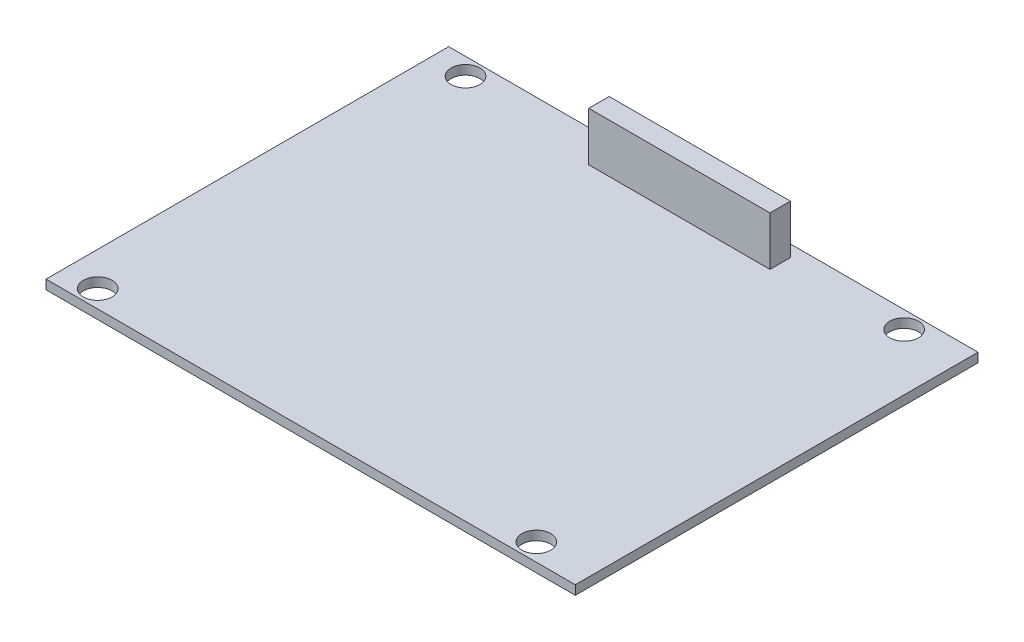
SolidWorks part; units mm, degrees
ref_plane "Front Plane" through (0, 0, 0) normal (0, 0, 1) x (1, 0, 0)
ref_plane "Top Plane" through (0, 0, 0) normal (0, 1, 0) x (1, 0, 0)
ref_plane "Right Plane" through (0, 0, 0) normal (1, 0, 0) x (0, 0, -1)
sketch "Sketch1" plane through (0, 0, 0) normal (0, 1, 0) x (1, 0, 0)
  line L1 (0, 0) -> (92, 0)
  line L2 (0, 0) -> (0, 70)
  line L3 (0, 70) -> (92, 70)
  line L4 (92, 0) -> (92, 70)
  circle A0 centre (5.92, 3.07) radius 2.5
  circle A1 centre (82.16, 3.07) radius 2.5
  circle A2 centre (82.16, 67) radius 2.5
  circle A3 centre (5.92, 67) radius 2.5
  dimension "D5" = 9.84
  dimension "D7" = 9.84
  dimension "D9" = 3
  dimension "D1" = 92
  dimension "D2" = 70
  dimension "D3" = 5.92
  dimension "D4" = 3.07
  dimension "D6" = 3.07
  dimension "D8" = 3
  dimension "D10" = 5.92
extrude "Y+ PCB extr" add sketch "Sketch1" along normal blind 1.6
sketch "Sketch2" plane through (0, 1.6, 0) normal (0, 1, 0) x (1, 0, 0)
  line L0 (92, 70) -> (0, 70) construction
  line L1 (29.95, 67.94) -> (61.45, 67.94)
  line L2 (29.95, 67.94) -> (29.95, 64.39)
  line L3 (29.95, 64.39) -> (61.45, 64.39)
  line L4 (61.45, 67.94) -> (61.45, 64.39)
  line L5 (0, 70) -> (0, 0) construction
  dimension "D1" = 2.06
  dimension "D2" = 29.95
  dimension "D3" = 31.5
  dimension "D4" = 3.55
extrude "Y+ header extr" add sketch "Sketch2" along normal blind 8.5
